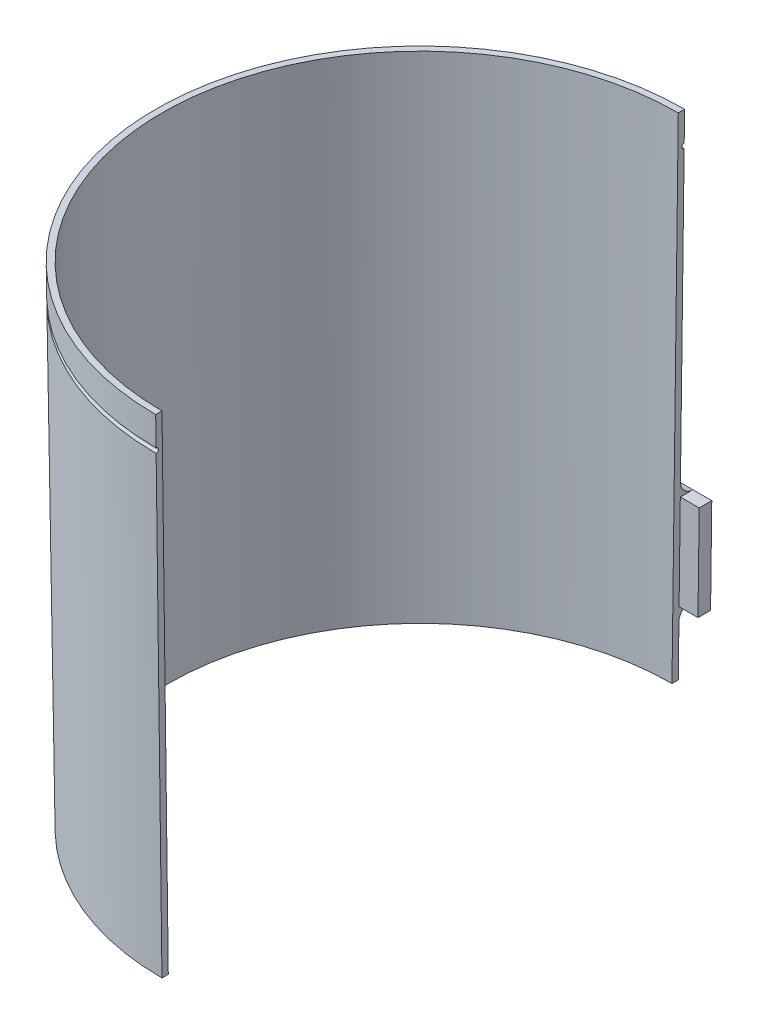
SolidWorks part; units mm, degrees
ref_plane "Front" through (0, 0, 0) normal (0, 0, 1) x (1, 0, 0)
ref_plane "Top" through (0, 0, 0) normal (0, 1, 0) x (1, 0, 0)
ref_plane "Right" through (0, 0, 0) normal (1, 0, 0) x (0, 0, -1)
sketch "Эскиз1" plane through (0, 0, 0) normal (0, 1, 0) x (1, 0, 0)
  line L0 (0, 40) -> (0, 41)
  line L1 (0, -40) -> (0, -41)
  arc A0 (0, 41) -> (0, -41) centre (0, 0) ccw
  arc A1 (0, 40) -> (0, -40) centre (0, 0) ccw
  dimension "D1" = 82
  dimension "D2" = 80
ref_plane "Плоскость1" through (0, 78, 0) normal (0, 1, 0) x (1, 0, 0)
sketch "Эскиз2" plane through (0, 78, 0) normal (0, 1, 0) x (1, 0, 0)
  line L0 (0, 42) -> (0, 41)
  line L1 (0, -41) -> (0, -42)
  arc A0 (0, 42) -> (0, -42) centre (0, 0) ccw
  arc A1 (0, 41) -> (0, -41) centre (0, 0) ccw
  dimension "D1" = 84
  dimension "D2" = 82
loft "По сечениям1" add profiles "Эскиз1", "Эскиз2" connector at (0, 0, -40) connector at (0, 78, -41)
ref_plane "Плоскость2" through (-40.9933, -0.5256, 0) normal (-0.9999, -0.0128, 0) x (0, 0, 1)
sketch "Эскиз3" plane through (-40.9933, -0.5256, 0) normal (-0.9999, -0.0128, 0) x (0, 0, 1)
  line L1 (-1.5, 2.0252) -> (1.5, 2.0252)
  line L2 (-1.5, 2.0252) -> (-1.5, 0.5252)
  line L3 (-1.5, 0.5252) -> (1.5, 0.5252)
  line L4 (1.5, 2.0252) -> (1.5, 0.5252)
  line L5 (-1.5, 2.0252) -> (1.5, 0.5252) construction
  line L6 (-1.5, 0.5252) -> (1.5, 2.0252) construction
  ellipse E0 centre (0, 0) end of major axis (41, 0) minor radius 0.5256 (41, 0) -> (-41, 0) ccw construction
  point P0 (0, 1.2752)
  dimension "D1" = 1.5
  dimension "D2" = 3
  dimension "D3" = 0
extrude "Бобышка-Вытянуть1" add sketch "Эскиз3" along normal blind 2 and the other way up to surface other way up to face at (0, 19.5, -20.75)
chamfer "Фаска1" distance 1.5 distance2 1 1 edges at (-42.9998, -0.026, 0) first distance on face at (-42.493, -0.0195, -0.375)
ref_plane "Плоскость3" through (-5, 0, 0) normal (1, 0, 0) x (0, 0, -1)
sketch "Эскиз4" plane through (-5, 0, 0) normal (1, 0, 0) x (0, 0, -1)
  line L0 (41.3205, 25) -> (43.3207, 25)
  line L2 (41, 0) -> (42, 78) construction
  line L3 (43.3207, 25) -> (43.1284, 10)
  line L4 (43.1284, 10) -> (41.1282, 10)
  line L5 (41.1282, 10) -> (41.3205, 25)
  dimension "D1" = 2
  dimension "D2" = 10
  dimension "D3" = 15
extrude "Бобышка-Вытянуть2" add sketch "Эскиз4" along normal blind 8 separate body
sketch "Эскиз5" plane through (0, -0.5512, -42.9931) normal (0, -0.0128, -0.9999) x (-1, 0, 0)
  line L0 (-3, 25.5533) -> (5, 25.5533) construction
  line L1 (0, 25.5533) -> (5, 25.5533)
  line L2 (0, 25.5533) -> (0, 10.4535)
  line L3 (0, 10.4535) -> (5, 10.4535)
  line L4 (5, 25.5533) -> (5, 10.4535)
  line L5 (0, 0.5256) -> (0, 78.532) construction
  line L6 (5, 50) -> (5, -50) construction
extrude "Бобышка-Вытянуть3" add sketch "Эскиз5" against normal up to next
fillet "Скругление1" radius 2 3 edges at (-2.5046, 9.9281, -41.0509) (-2.5046, 25.0266, -41.2449)
ref_axis "Ось1" through (0, -0.0001, 0) along (0, -1, 0)
sketch "Эскиз6" plane through (0, 0, 0) normal (1, 0, 0) x (0, 0, -1)
  line L0 (-41, 0) -> (-42, 78) construction
  line L1 (-42, 78) -> (-41, 78) construction
  circle A0 centre (-41.9359, 73) radius 0.375
  dimension "D1" = 0.75
  dimension "D2" = 0
  dimension "D3" = 5
revolve "Вырез-Повернуть1" cut sketch "Эскиз6" angle 360 about axis through (0, -0.0001, 0) along (0, -1, 0)
